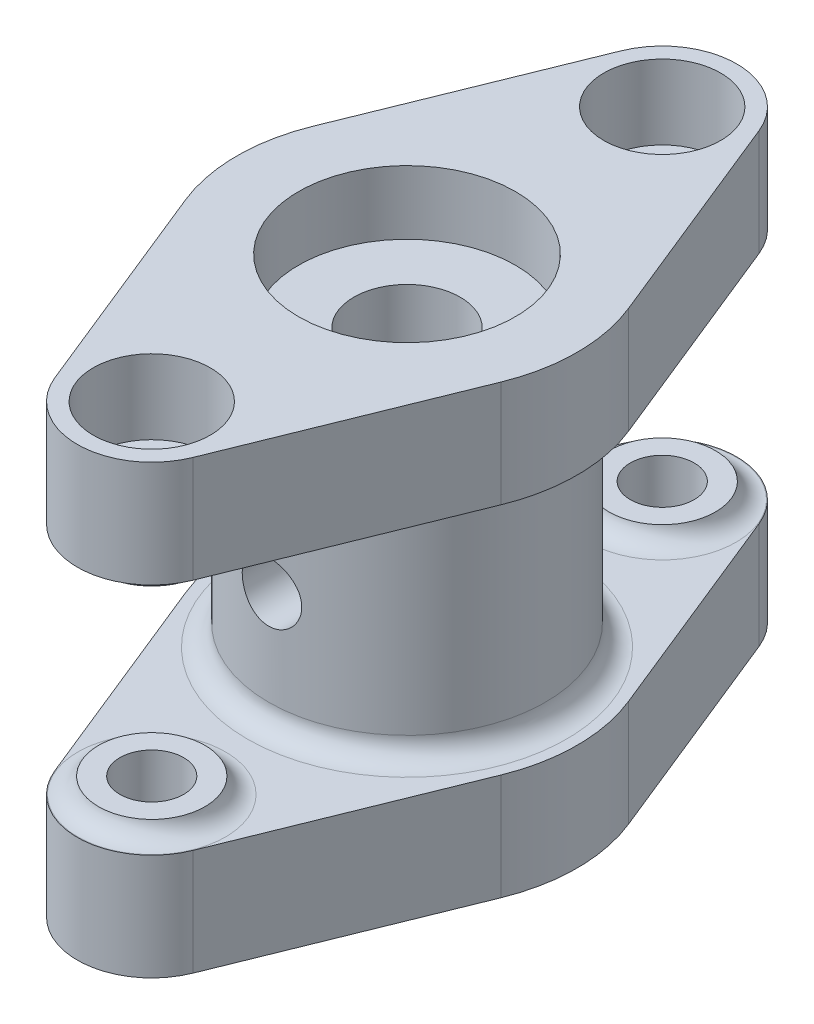
SolidWorks part; units mm, degrees
ref_plane "Front Plane" through (0, 0, 0) normal (0, 0, 1) x (1, 0, 0)
ref_plane "Top Plane" through (0, 0, 0) normal (0, 1, 0) x (1, 0, 0)
ref_plane "Right Plane" through (0, 0, 0) normal (1, 0, 0) x (0, 0, -1)
sketch "Sketch1" plane through (0, 0, 0) normal (0, 1, 0) x (1, 0, 0)
  line L0 (-15.75, 15.5) -> (15.75, 15.5) construction
  line L6 (-15.75, 0) -> (-15.75, 15.5) construction
  line L7 (15.75, 0) -> (15.75, 15.5) construction
  line L8 (-15.75, 13.5) -> (15.75, 13.5) construction
  line L9 (-3.2446, 13.3125) -> (-7.4162, 3)
  line L10 (-1.4309, -2.05) -> (1.4309, -2.05)
  line L11 (-3.2446, -13.3125) -> (-7.4162, -3)
  line L12 (3.2446, -13.3125) -> (7.4162, -3)
  line L13 (3.2446, 13.3125) -> (7.4162, 3)
  circle A0 centre (0, 0) radius 15.75 construction
  arc A1 (1.4309, -2.05) -> (-1.4309, -2.05) centre (0, 0) ccw
  circle A3 centre (0, 12) radius 1.5
  circle A6 centre (0, -12) radius 1.5
  circle A8 centre (0, 12) radius 5 construction
  arc A12 (3.2446, 13.3125) -> (-3.2446, 13.3125) centre (0, 12) ccw
  arc A24 (-3.2446, -13.3125) -> (3.2446, -13.3125) centre (0, -12) ccw
  circle A25 centre (0, 0) radius 17 construction
  arc A27 (-7.4162, 3) -> (-7.4162, -3) centre (0, 0) ccw
  arc A28 (7.4162, -3) -> (7.4162, 3) centre (0, 0) ccw
  point P3 (-7.686, 3.4072)
  point P5 (3.4585, -12.7765)
  point P14 (0, -12.25)
  point P15 (0, -12.25)
  point P23 (0, 0)
  point P25 (0, 0)
  point P26 (0, 0)
  point P27 (3.2446, -11.8584)
  point P43 (0, 0)
  dimension "D1" = 31.5
  dimension "D2" = 5
  dimension "D3" = 3
  dimension "D4" = 10
  dimension "D5" = 2
  dimension "D6" = 8
  dimension "D7" = 2.05
  dimension "D8" = 34
extrude "Boss-Extrude1" add sketch "Sketch1" along normal blind 5
sketch "Sketch2" plane through (0, 5, 0) normal (0, 1, 0) x (1, 0, 0)
  line L0 (-1.4309, -2.05) -> (1.4309, -2.05) construction
  line L1 (-1.4309, -2.05) -> (1.4309, -2.05)
  circle A0 centre (0, 0) radius 6.5
  circle A2 centre (0, 12) radius 5 construction
  arc A3 (1.4309, -2.05) -> (-1.4309, -2.05) centre (0, 0) ccw construction
  arc A4 (1.4309, -2.05) -> (-1.4309, -2.05) centre (0, 0) ccw
  dimension "D1" = 13
  dimension "D3" = 10
extrude "Boss-Extrude2" add sketch "Sketch2" along normal blind 11
sketch "Sketch3" plane through (0, 16, 0) normal (0, 1, 0) x (1, 0, 0)
  line L0 (-1.4309, -2.05) -> (1.4309, -2.05) construction
  line L1 (-1.4309, -2.05) -> (1.4309, -2.05)
  line L6 (-3.2446, 13.3125) -> (-7.4162, 3)
  line L7 (-3.2446, 13.3125) -> (-7.4162, 3)
  line L8 (-7.4162, -3) -> (-3.2446, -13.3125)
  line L9 (-7.4162, -3) -> (-3.2446, -13.3125)
  line L10 (3.2446, -13.3125) -> (7.4162, -3)
  line L11 (3.2446, -13.3125) -> (7.4162, -3)
  line L12 (7.4162, 3) -> (3.2446, 13.3125)
  line L13 (7.4162, 3) -> (3.2446, 13.3125)
  circle A1 centre (0, -12) radius 1.5 construction
  arc A10 (-7.4162, 3) -> (-7.4162, -3) centre (0, 0) ccw
  arc A12 (-7.4162, 3) -> (-7.4162, -3) centre (0, 0) ccw
  circle A17 centre (0, 12) radius 1.5 construction
  circle A18 centre (0, -12) radius 1.5
  circle A22 centre (0, 12) radius 1.5
  arc A23 (3.2446, 13.3125) -> (-3.2446, 13.3125) centre (0, 12) ccw
  arc A24 (7.4162, -3) -> (7.4162, 3) centre (0, 0) ccw
  arc A25 (7.4162, -3) -> (7.4162, 3) centre (0, 0) ccw
  arc A27 (-3.2446, -13.3125) -> (3.2446, -13.3125) centre (0, -12) ccw
  arc A33 (3.2446, 13.3125) -> (-3.2446, 13.3125) centre (0, 12) ccw
  arc A37 (-3.2446, -13.3125) -> (3.2446, -13.3125) centre (0, -12) ccw
  arc A45 (1.4309, -2.05) -> (-1.4309, -2.05) centre (0, 0) ccw construction
  arc A46 (1.4309, -2.05) -> (-1.4309, -2.05) centre (0, 0) ccw
  dimension "D1" = 0
extrude "Boss-Extrude3" add sketch "Sketch3" along normal blind 5
sketch "Sketch4" plane through (0, 0, 0) normal (0, 0, 1) x (1, 0, 0)
  line L0 (0, 0) -> (0, 21) construction
  line L3 (3.2446, 21) -> (-3.2446, 21) construction
  circle A0 centre (0, 10.5) radius 1.4
  point P2 (0, 0)
  point P4 (0, 0)
  point P5 (0, 21)
  point P10 (0, 0)
  dimension "D1" = 2.8
extrude "Cut-Extrude1" cut sketch "Sketch4" along normal through all
fillet "Fillet1" radius 1 2 edges at (0, 16, 6.5) (0, 5, 6.5)
sketch "Sketch6" plane through (0, 0, 0) normal (0, -1, 0) x (1, 0, 0)
  line L17 (2.75, -13.5877) -> (2.75, -10.4123)
  line L18 (2.75, -10.4123) -> (0, -8.8246)
  line L19 (0, -8.8246) -> (-2.75, -10.4123)
  line L20 (-2.75, -10.4123) -> (-2.75, -13.5877)
  line L21 (-2.75, -13.5877) -> (0, -15.1754)
  line L22 (0, -15.1754) -> (2.75, -13.5877)
  line L34 (55, 0) -> (-55, 0) construction
  line L35 (0, 15.1754) -> (2.75, 13.5877)
  line L36 (-2.75, 13.5877) -> (0, 15.1754)
  line L37 (-2.75, 10.4123) -> (-2.75, 13.5877)
  line L38 (0, 8.8246) -> (-2.75, 10.4123)
  line L39 (2.75, 10.4123) -> (0, 8.8246)
  line L40 (2.75, 13.5877) -> (2.75, 10.4123)
  circle A0 centre (0, -12) radius 2.75 construction
  circle A1 centre (0, 12) radius 2.75 construction
  point P1 (0, 0)
  point P8 (-11.4127, -3.7082)
  point P20 (0, 0)
  point P45 (0, 0)
  dimension "D1" = 5.5
extrude "Cut-Extrude2" cut sketch "Sketch6" against normal blind 3
sketch "Sketch8" plane through (0, 5, 0) normal (0, 1, 0) x (1, 0, 0)
  circle A0 centre (0, -12) radius 2.5
  circle A1 centre (0, -12) radius 1.5 construction
  circle A2 centre (0, -12) radius 1.5
  circle A5 centre (0, 12) radius 2.5
  circle A6 centre (0, 12) radius 1.5
  circle A12 centre (-8.7185, 0) radius 2.5 [skipped]
  circle A13 centre (-8.7185, 0) radius 1.5 [skipped]
  circle A14 centre (14.1068, -7.4164) radius 2.5 [skipped]
  circle A15 centre (14.1068, -7.4164) radius 1.5 [skipped]
  circle A16 centre (14.1068, 7.4164) radius 2.5 [skipped]
  circle A17 centre (14.1068, 7.4164) radius 1.5 [skipped]
  point P2 (0, 12)
  point P6 (0, -12.0141)
  point P24 (3.899, 0)
  dimension "D1" = 5
  dimension "D2" = 5
extrude "Boss-Extrude5" add sketch "Sketch8" along normal blind 0.75
fillet "Fillet4" radius 1 2 edges at (0, 5, -9.5) (0, 5, 14.5)
sketch "Sketch9" plane through (0, 16, 0) normal (0, -1, 0) x (1, 0, 0)
  circle A0 centre (0, -12) radius 2.5
  circle A1 centre (0, -12) radius 1.5 construction
  circle A2 centre (0, -12) radius 1.5
  circle A3 centre (0, 12) radius 2.5
  circle A4 centre (0, 12) radius 1.5
  circle A12 centre (0, 12) radius 1.5 construction
  point P6 (0, 0)
  point P7 (-0.0006, 12.2287)
  point P8 (0, 0)
  point P9 (0, 11.8112)
  point P25 (-0.0006, 0)
  dimension "D1" = 5
  dimension "D2" = 2
extrude "Boss-Extrude6" add sketch "Sketch9" along normal blind 0.75
fillet "Fillet5" radius 1 2 edges at (0, 16, 14.5) (0, 16, -9.5)
sketch "Sketch12" plane through (0, 21, 0) normal (0, 1, 0) x (1, 0, 0)
  circle A0 centre (0, 12) radius 2.75
  circle A1 centre (0, -12) radius 2.75
  point P3 (0, -12)
  point P13 (0, 0)
  dimension "D1" = 5.5
  dimension "D2" = 2
extrude "Cut-Extrude5" cut sketch "Sketch12" against normal offset from surface (3.5 mm away) 1.5 up to face at (0, 16, 15.4682)
sketch "Sketch10" plane through (0, 21, 0) normal (0, 1, 0) x (1, 0, 0)
  circle A0 centre (0, 0) radius 5.1
  dimension "D1" = 10.2
extrude "Cut-Extrude3" cut sketch "Sketch10" against normal blind 3
sketch "Sketch11" plane through (0, 0, 0) normal (0, -1, 0) x (1, 0, 0)
  circle A0 centre (0, 0) radius 5.1
  dimension "D1" = 10.2
extrude "Cut-Extrude4" cut sketch "Sketch11" against normal blind 3.5
